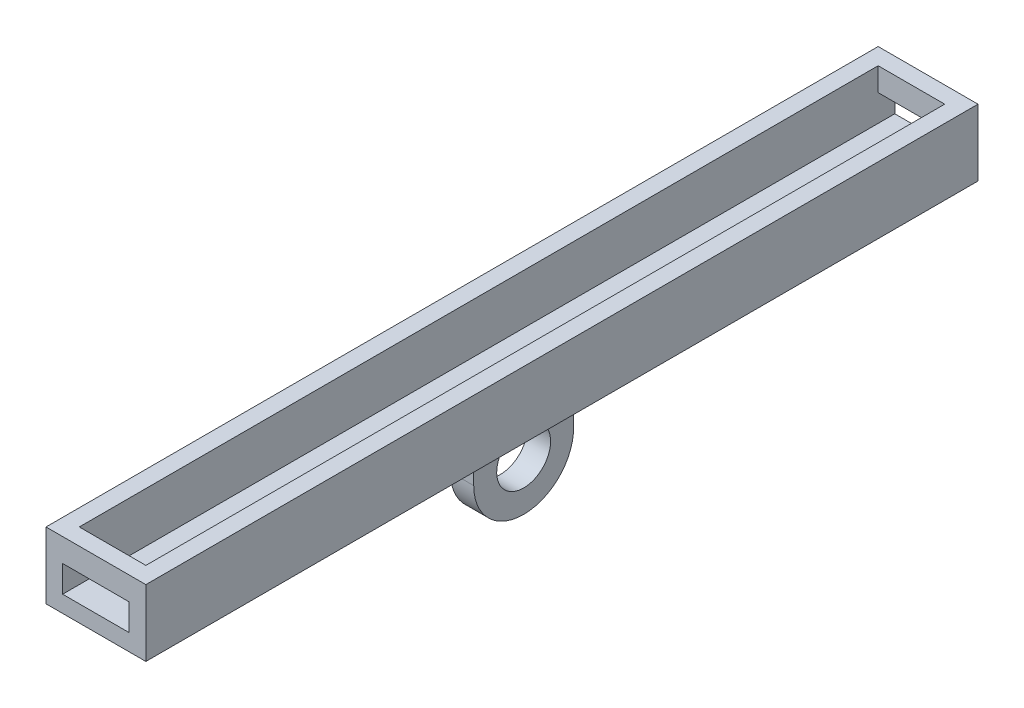
SolidWorks part; units mm, degrees
ref_plane "Front Plane" through (0, 0, 0) normal (0, 0, 1) x (1, 0, 0)
ref_plane "Top Plane" through (0, 0, 0) normal (0, 1, 0) x (1, 0, 0)
ref_plane "Right Plane" through (0, 0, 0) normal (1, 0, 0) x (0, 0, -1)
sketch "Sketch1" plane through (0, 0, 0) normal (0, 0, 1) x (1, 0, 0)
  line L0 (25, 20) -> (30, 20)
  line L1 (0, 0) -> (30, 0)
  line L2 (0, 0) -> (0, 20)
  line L3 (0, 20) -> (5, 20)
  line L4 (30, 0) -> (30, 20)
  line L6 (5, 20) -> (5, 5)
  line L7 (5, 5) -> (25, 5)
  line L8 (25, 20) -> (25, 5)
  dimension "D1" = 20
  dimension "D2" = 5
  dimension "D3" = 5
  dimension "D4" = 5
  dimension "D5" = 15
extrude "Boss-Extrude1" add sketch "Sketch1" along normal blind 250
sketch "Sketch2" plane through (30, 0, 0) normal (1, 0, 0) x (0, 0, -1)
  line L5 (-250, 0) -> (0, 0) construction
  line L6 (-140, -15) -> (-140, -10)
  line L7 (-110, -15) -> (-110, -10)
  line L10 (-150, 0) -> (-100, 0)
  circle A0 centre (-125, -15) radius 8.1
  arc A1 (-140, -15) -> (-110, -15) centre (-125, -15) ccw
  arc A2 (-110, -10) -> (-100, 0) centre (-100, -10) cw
  arc A3 (-140, -10) -> (-150, 0) centre (-150, -10) ccw
  point P4 (-125, 0)
  point P11 (-85, 0)
  point P14 (-115, 0)
  dimension "D2" = 16.2
  dimension "D3" = 10
  dimension "D4" = 15
  dimension "D1" = 15
  dimension "D5" = 50
extrude "Boss-Extrude2" add sketch "Sketch2" against normal blind 7 from offset 11.5 offset against normal yes
sketch "Sketch3" plane through (30, 0, 0) normal (1, 0, 0) x (0, 0, -1)
  line L0 (-250, 0) -> (0, 0) construction
  line L1 (-225, 0) -> (-215, 0)
  line L2 (-225, 0) -> (-225, -10)
  line L3 (-225, -10) -> (-215, -10)
  line L4 (-215, 0) -> (-215, -10)
  line L5 (-250, 0) -> (-250, 20) construction
  circle A0 centre (-220, -5) radius 1.75
  point P7 (0, 0)
  point P8 (-243.6478, 0)
  dimension "D2" = 3.5
  dimension "D1" = 5
  dimension "D3" = 5
  dimension "D4" = 10
  dimension "D5" = 10
  dimension "D6" = 25
extrude "Boss-Extrude3" add sketch "Sketch3" along normal blind 7 from offset 17.1 offset against normal yes
fillet "Fillet1" radius 5 2 edges at (16.4, -10, 215) (16.4, -10, 225)
sketch "Sketch5" plane through (0, 5, 0) normal (0, 1, 0) x (1, 0, 0)
  line L0 (25, -250) -> (5, -250) construction
  line L1 (5, -125) -> (25, -125) construction
  line L2 (5, -250) -> (5, 0) construction
  line L3 (25, -250) -> (25, 0) construction
  circle A0 centre (15, -230) radius 1.5
  circle A1 centre (15, -210) radius 1.5
  circle A2 centre (15, -40) radius 1.5
  circle A3 centre (15, -20) radius 1.5
  point P8 (15, -250)
  dimension "D3" = 3
  dimension "D1" = 20
  dimension "D2" = 20
extrude "Cut-Extrude1" cut sketch "Sketch5" against normal blind 7
sketch "Sketch6" plane through (0, 20, 0) normal (0, 1, 0) x (1, 0, 0)
  line L0 (25, -250) -> (25, 0) construction
  line L1 (5, 0) -> (25, 0)
  line L2 (5, 0) -> (5, -5)
  line L3 (5, -5) -> (25, -5)
  line L4 (25, 0) -> (25, -5)
  line L5 (25, -250) -> (25, 0) construction
  line L6 (5, -250) -> (25, -250)
  line L7 (5, -250) -> (5, -245)
  line L8 (5, -245) -> (25, -245)
  line L9 (25, -250) -> (25, -245)
  dimension "D1" = 5
  dimension "D2" = 5
extrude "Boss-Extrude4" add sketch "Sketch6" against normal blind 7
